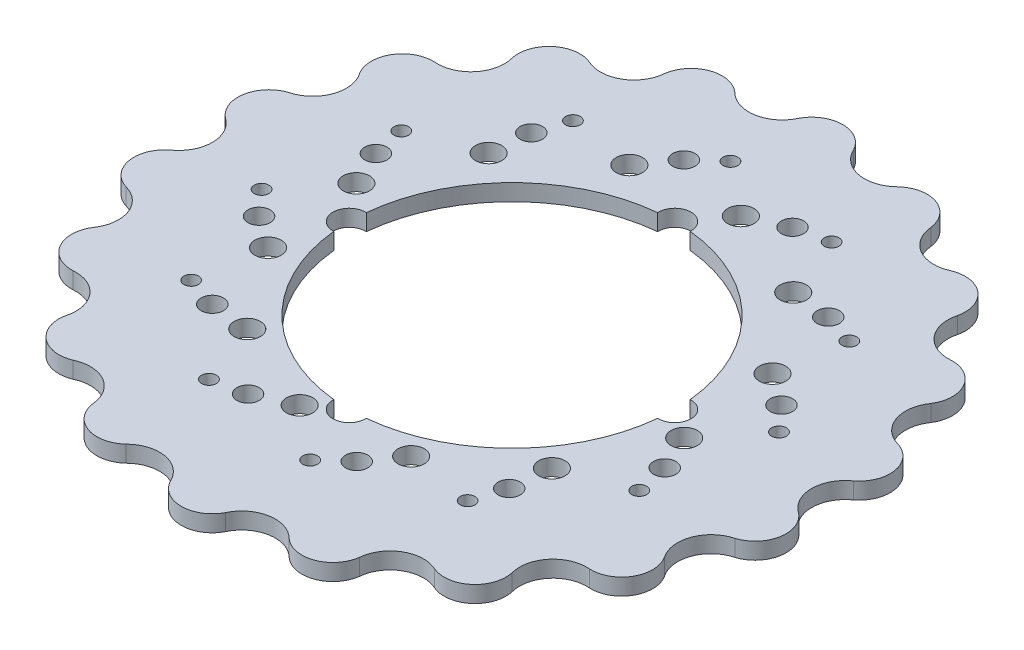
SolidWorks part; units mm, degrees
ref_plane "Front Plane" through (0, 0, 0) normal (0, 0, 1) x (1, 0, 0)
ref_plane "Top Plane" through (0, 0, 0) normal (0, 1, 0) x (1, 0, 0)
ref_plane "Right Plane" through (0, 0, 0) normal (1, 0, 0) x (0, 0, -1)
sketch "Sketch2" plane through (0, 0, 0) normal (0, 1, 0) x (1, 0, 0)
  line L0 (0, 0) -> (0, 101.6) construction
  line L1 (0, 0) -> (34.7492, 95.4728) construction
  line L2 (0, 0) -> (17.6427, 100.0565) construction
  line L3 (0, 0) -> (8.855, 101.2134) construction
  line L4 (26.296, 98.1381) -> (0, 0) construction
  circle A0 centre (0, 0) radius 101.6
  circle A1 centre (0, 0) radius 92.075
  circle A2 centre (0, 0) radius 96.8375
  arc A3 (0, 101.6) -> (8.4399, 96.469) centre (0, 92.0931) cw
  arc A4 (8.4399, 96.469) -> (15.9887, 90.6762) centre (17.7777, 100.8223) ccw
  arc A5 (25.0634, 93.5378) -> (15.9887, 90.6762) centre (17.7777, 100.8223) cw
  arc A6 (34.7492, 95.4728) -> (25.0634, 93.5378) centre (31.4977, 86.5392) ccw
  arc A7 (34.7492, 95.4728) -> (40.9253, 87.7646) centre (31.4977, 86.5392) cw
  arc A8 (40.9253, 87.7646) -> (46.0375, 79.7393) centre (51.1888, 88.6617) ccw
  arc A9 (55.5437, 79.3246) -> (46.0375, 79.7393) centre (51.1888, 88.6617) cw
  arc A10 (65.3072, 77.8301) -> (55.5437, 79.3246) centre (59.1963, 70.5474) ccw
  arc A11 (65.3072, 77.8301) -> (68.4745, 68.4745) centre (59.1963, 70.5474) cw
  arc A12 (68.4745, 68.4745) -> (70.5335, 59.1847) centre (78.4258, 65.8071) ccw
  arc A13 (79.3246, 55.5437) -> (70.5335, 59.1847) centre (78.4258, 65.8071) cw
  arc A14 (87.9882, 50.8) -> (79.3246, 55.5437) centre (79.755, 46.0465) ccw
  arc A15 (87.9882, 50.8) -> (87.7646, 40.9253) centre (79.755, 46.0465) cw
  arc A16 (87.7646, 40.9253) -> (86.5222, 31.4915) centre (96.2035, 35.0152) ccw
  arc A17 (93.5378, 25.0634) -> (86.5222, 31.4915) centre (96.2035, 35.0152) cw
  arc A18 (100.0565, 17.6427) -> (93.5378, 25.0634) centre (90.694, 15.9918) ccw
  arc A19 (100.0565, 17.6427) -> (96.469, 8.4399) centre (90.694, 15.9918) cw
  arc A20 (96.469, 8.4399) -> (92.075, 0) centre (102.3777, 0) ccw
  arc A21 (96.469, -8.4399) -> (92.075, 0) centre (102.3777, 0) cw
  arc A22 (100.0565, -17.6427) -> (96.469, -8.4399) centre (90.694, -15.9918) ccw
  arc A23 (100.0565, -17.6427) -> (93.5378, -25.0634) centre (90.694, -15.9918) cw
  arc A24 (93.5378, -25.0634) -> (86.5222, -31.4915) centre (96.2035, -35.0152) ccw
  arc A25 (87.7646, -40.9253) -> (86.5222, -31.4915) centre (96.2035, -35.0152) cw
  arc A26 (87.9882, -50.8) -> (87.7646, -40.9253) centre (79.755, -46.0465) ccw
  arc A27 (87.9882, -50.8) -> (79.3246, -55.5437) centre (79.755, -46.0465) cw
  arc A28 (79.3246, -55.5437) -> (70.5335, -59.1847) centre (78.4258, -65.8071) ccw
  arc A29 (68.4745, -68.4745) -> (70.5335, -59.1847) centre (78.4258, -65.8071) cw
  arc A30 (65.3072, -77.8301) -> (68.4745, -68.4745) centre (59.1963, -70.5474) ccw
  arc A31 (65.3072, -77.8301) -> (55.5437, -79.3246) centre (59.1963, -70.5474) cw
  arc A32 (55.5437, -79.3246) -> (46.0375, -79.7393) centre (51.1888, -88.6617) ccw
  arc A33 (40.9253, -87.7646) -> (46.0375, -79.7393) centre (51.1888, -88.6617) cw
  arc A34 (34.7492, -95.4728) -> (40.9253, -87.7646) centre (31.4977, -86.5392) ccw
  arc A35 (34.7492, -95.4728) -> (25.0634, -93.5378) centre (31.4977, -86.5392) cw
  arc A36 (25.0634, -93.5378) -> (15.9887, -90.6762) centre (17.7777, -100.8223) ccw
  arc A37 (8.4399, -96.469) -> (15.9887, -90.6762) centre (17.7777, -100.8223) cw
  arc A38 (0, -101.6) -> (8.4399, -96.469) centre (0, -92.0931) ccw
  arc A39 (0, -101.6) -> (-8.4399, -96.469) centre (0, -92.0931) cw
  arc A40 (-8.4399, -96.469) -> (-15.9887, -90.6762) centre (-17.7777, -100.8223) ccw
  arc A41 (-25.0634, -93.5378) -> (-15.9887, -90.6762) centre (-17.7777, -100.8223) cw
  arc A42 (-34.7492, -95.4728) -> (-25.0634, -93.5378) centre (-31.4977, -86.5392) ccw
  arc A43 (-34.7492, -95.4728) -> (-40.9253, -87.7646) centre (-31.4977, -86.5392) cw
  arc A44 (-40.9253, -87.7646) -> (-46.0375, -79.7393) centre (-51.1888, -88.6617) ccw
  arc A45 (-55.5437, -79.3246) -> (-46.0375, -79.7393) centre (-51.1888, -88.6617) cw
  arc A46 (-65.3072, -77.8301) -> (-55.5437, -79.3246) centre (-59.1963, -70.5474) ccw
  arc A47 (-65.3072, -77.8301) -> (-68.4745, -68.4745) centre (-59.1963, -70.5474) cw
  arc A48 (-68.4745, -68.4745) -> (-70.5335, -59.1847) centre (-78.4258, -65.8071) ccw
  arc A49 (-79.3246, -55.5437) -> (-70.5335, -59.1847) centre (-78.4258, -65.8071) cw
  arc A50 (-87.9882, -50.8) -> (-79.3246, -55.5437) centre (-79.755, -46.0465) ccw
  arc A51 (-87.9882, -50.8) -> (-87.7646, -40.9253) centre (-79.755, -46.0465) cw
  arc A52 (-87.7646, -40.9253) -> (-86.5222, -31.4915) centre (-96.2035, -35.0152) ccw
  arc A53 (-93.5378, -25.0634) -> (-86.5222, -31.4915) centre (-96.2035, -35.0152) cw
  arc A54 (-100.0565, -17.6427) -> (-93.5378, -25.0634) centre (-90.694, -15.9918) ccw
  arc A55 (-100.0565, -17.6427) -> (-96.469, -8.4399) centre (-90.694, -15.9918) cw
  arc A56 (-96.469, -8.4399) -> (-92.075, 0) centre (-102.3777, 0) ccw
  arc A57 (-96.469, 8.4399) -> (-92.075, 0) centre (-102.3777, 0) cw
  arc A58 (-100.0565, 17.6427) -> (-96.469, 8.4399) centre (-90.694, 15.9918) ccw
  arc A59 (-100.0565, 17.6427) -> (-93.5378, 25.0634) centre (-90.694, 15.9918) cw
  arc A60 (-93.5378, 25.0634) -> (-86.5222, 31.4915) centre (-96.2035, 35.0152) ccw
  arc A61 (-87.7646, 40.9253) -> (-86.5222, 31.4915) centre (-96.2035, 35.0152) cw
  arc A62 (-87.9882, 50.8) -> (-87.7646, 40.9253) centre (-79.755, 46.0465) ccw
  arc A63 (-87.9882, 50.8) -> (-79.3246, 55.5437) centre (-79.755, 46.0465) cw
  arc A64 (-79.3246, 55.5437) -> (-70.5335, 59.1847) centre (-78.4258, 65.8071) ccw
  arc A65 (-68.4745, 68.4745) -> (-70.5335, 59.1847) centre (-78.4258, 65.8071) cw
  arc A66 (-65.3072, 77.8301) -> (-68.4745, 68.4745) centre (-59.1963, 70.5474) ccw
  arc A67 (-65.3072, 77.8301) -> (-55.5437, 79.3246) centre (-59.1963, 70.5474) cw
  arc A68 (-55.5437, 79.3246) -> (-46.0375, 79.7393) centre (-51.1888, 88.6617) ccw
  arc A69 (-40.9253, 87.7646) -> (-46.0375, 79.7393) centre (-51.1888, 88.6617) cw
  arc A70 (-34.7492, 95.4728) -> (-40.9253, 87.7646) centre (-31.4977, 86.5392) ccw
  arc A71 (-34.7492, 95.4728) -> (-25.0634, 93.5378) centre (-31.4977, 86.5392) cw
  arc A72 (-25.0634, 93.5378) -> (-15.9887, 90.6762) centre (-17.7777, 100.8223) ccw
  arc A73 (-8.4399, 96.469) -> (-15.9887, 90.6762) centre (-17.7777, 100.8223) cw
  arc A74 (0, 101.6) -> (-8.4399, 96.469) centre (0, 92.0931) ccw
  point P10 (8.4399, 96.469)
  point P11 (25.0634, 93.5378)
  point P12 (15.9887, 90.6762)
  point P175 (0, 0)
  dimension "D1" = 203.2
  dimension "D2" = 184.15
  dimension "D5" = 193.675
  dimension "D4" = 18
  dimension "D3" = 20
  dimension "D6" = 5
  dimension "D7" = 5
extrude "Boss-Extrude1" add sketch "Sketch2" along normal blind 5.08 contours A67 A66 A2 | A68 A2 A65 A1 | A71 A70 A2 | A72 A2 A69 A1 | A2 A73 A1 A4 | A3 A74 A2 | A8 A2 A5 A1 | A7 A6 A2 | A11 A10 A2 | A12 A2 A9 A1 | A16 A2 A13 A1 | A15 A14 A2 | A20 A2 A17 A1 | A19 A18 A2 | A24 A2 A21 A1 | A23 A22 A2 | A28 A2 A25 A1 | A27 A26 A2 | A32 A2 A29 A1 | A31 A30 A2 | A36 A2 A33 A1 | A35 A34 A2 | A40 A2 A37 A1 | A39 A38 A2 | A44 A2 A41 A1 | A43 A42 A2 | A48 A2 A45 A1 | A47 A46 A2 | A52 A2 A49 A1 | A51 A50 A2 | A1 | A55 A54 A2 | A59 A58 A2 | A63 A62 A2 | A64 A2 A61 A1 | A60 A2 A57 A1 | A56 A2 A53 A1 region at (97.2191, 0, -17.1424) region at (97.2191, 0, 17.1424) region at (85.4931, 0, -49.3595) region at (92.5977, 0, -16.3275) region at (85.4931, 0, 49.3595) region at (92.5977, 0, 16.3275) region at (63.4553, 0, -75.6231) region at (81.429, 0, -47.0131) region at (0, 0, 0) region at (63.4553, 0, 75.6231) region at (81.429, 0, 47.0131) region at (33.7639, 0, -92.7654) region at (60.4389, 0, -72.0282) region at (33.7639, 0, 92.7654) region at (60.4389, 0, 72.0282) region at (0, 0, -98.7189) region at (32.1588, 0, -88.3557) region at (0, 0, 98.7189) region at (32.1588, 0, 88.3557) region at (-33.7639, 0, -92.7654) region at (0, 0, -94.0262) region at (-33.7639, 0, 92.7654) region at (0, 0, 94.0262) region at (-63.4553, 0, -75.6231) region at (-32.1588, 0, -88.3557) region at (-63.4553, 0, 75.6231) region at (-32.1588, 0, 88.3557) region at (-85.4931, 0, -49.3595) region at (-60.4389, 0, -72.0282) region at (-85.4931, 0, 49.3595) region at (-60.4389, 0, 72.0282) region at (-97.2191, 0, -17.1424) region at (-81.429, 0, -47.0131) region at (-97.2191, 0, 17.1424) region at (-81.429, 0, 47.0131) region at (-92.5977, 0, -16.3275) region at (-92.5977, 0, 16.3275)
sketch "Sketch3" plane through (0, 5.08, 0) normal (0, 1, 0) x (1, 0, 0)
  circle A0 centre (0, 0) radius 50
  circle A1 centre (0, 50) radius 5
  circle A2 centre (50, 0) radius 5
  circle A3 centre (0, -50) radius 5
  circle A4 centre (-50, 0) radius 5
  point P13 (0, 0)
  dimension "D1" = 4
  dimension "D2" = 10
extrude "Cut-Extrude1" cut sketch "Sketch3" against normal through all contours A0 A1 | A0 A1 | A0 A4 | A0 A4 | A0 A2 | A0 A2 | A0 A3 | A0 A3 | A0 region at (47.8335, 5.08, 0) region at (52.0764, 5.08, 0) region at (0, 5.08, -47.8335) region at (0, 5.08, -52.0764) region at (0, 5.08, 52.0764) region at (0, 5.08, 47.8335) region at (-47.8335, 5.08, 0) region at (-52.0764, 5.08, 0)
sketch "Sketch4" plane through (0, 5.08, 0) normal (0, 1, 0) x (1, 0, 0)
  arc A0 (0, 55) -> (39.6875, 68.7408) centre (35.1097, 17.7778) cw construction
  circle A3 centre (8.7092, 61.6093) radius 4.0351
  circle A4 centre (19.6365, 66.5504) radius 3.4245
  circle A5 centre (29.5538, 68.6434) radius 2.2596
  circle A6 centre (37.077, 49.3409) radius 4.0351
  circle A7 centre (49.0109, 48.1563) radius 3.4245
  circle A8 centre (58.646, 45.0104) radius 2.2596
  circle A9 centre (55.5101, 24.5322) radius 4.0351
  circle A10 centre (65.2529, 17.5394) radius 3.4245
  circle A11 centre (72.0241, 9.9974) radius 2.2596
  circle A12 centre (59.0693, -6.1692) radius 4.0351
  circle A13 centre (64.0104, -17.0965) radius 3.4245
  circle A14 centre (66.1034, -27.0138) radius 2.2596
  circle A15 centre (46.8009, -34.537) radius 4.0351
  circle A16 centre (45.6163, -46.4709) radius 3.4245
  circle A17 centre (42.4704, -56.106) radius 2.2596
  circle A18 centre (21.9922, -52.9701) radius 4.0351
  circle A19 centre (14.9994, -62.7129) radius 3.4245
  circle A20 centre (7.4574, -69.4841) radius 2.2596
  circle A21 centre (-8.7092, -56.5293) radius 4.0351
  circle A22 centre (-19.6365, -61.4704) radius 3.4245
  circle A23 centre (-29.5538, -63.5634) radius 2.2596
  circle A24 centre (-37.077, -44.2609) radius 4.0351
  circle A25 centre (-49.0109, -43.0763) radius 3.4245
  circle A26 centre (-58.646, -39.9304) radius 2.2596
  circle A27 centre (-55.5101, -19.4522) radius 4.0351
  circle A28 centre (-65.2529, -12.4594) radius 3.4245
  circle A29 centre (-72.0241, -4.9174) radius 2.2596
  circle A30 centre (-59.0693, 11.2492) radius 4.0351
  circle A31 centre (-64.0104, 22.1765) radius 3.4245
  circle A32 centre (-66.1034, 32.0938) radius 2.2596
  circle A33 centre (-46.8009, 39.617) radius 4.0351
  circle A34 centre (-45.6163, 51.5509) radius 3.4245
  circle A35 centre (-42.4704, 61.186) radius 2.2596
  circle A36 centre (-21.9922, 58.0501) radius 4.0351
  circle A37 centre (-14.9994, 67.7929) radius 3.4245
  circle A38 centre (-7.4574, 74.5641) radius 2.2596
  point P83 (0, 2.54)
  dimension "D1" = 12
extrude "Cut-Extrude3" cut sketch "Sketch4" against normal through all
